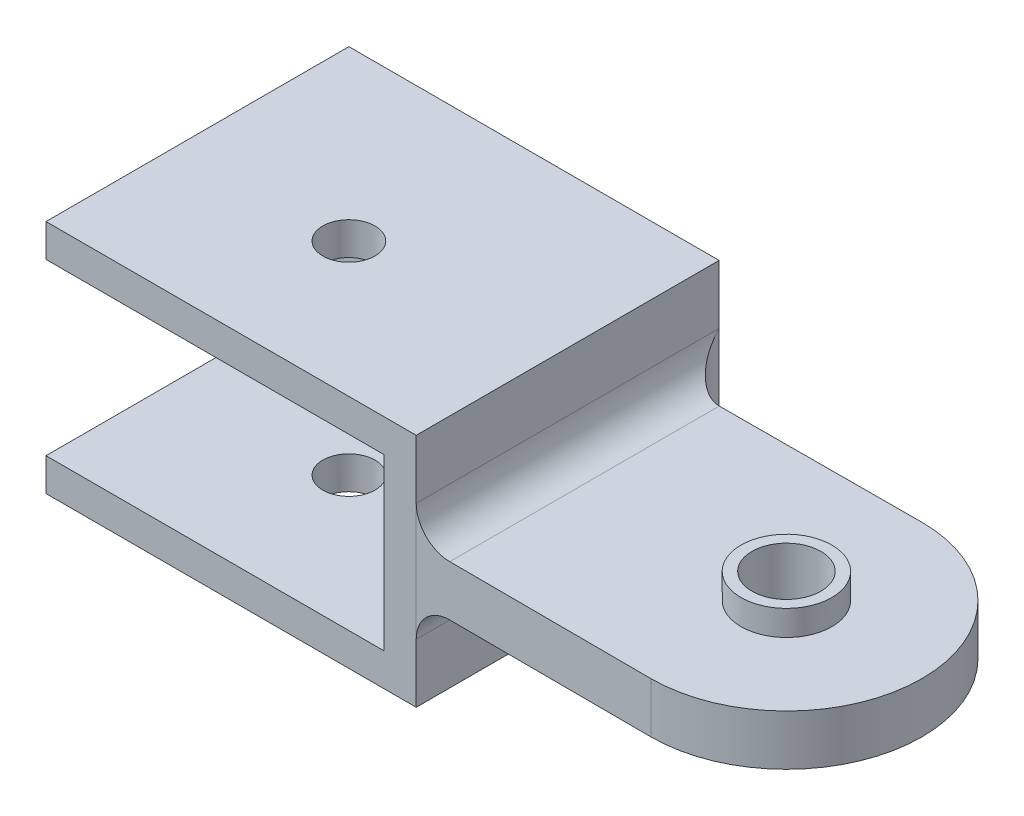
SolidWorks part; units mm, degrees
material "1060 Alloy"
ref_plane "Front Plane" through (0, 0, 0) normal (0, 0, 1) x (1, 0, 0)
ref_plane "Top Plane" through (0, 0, 0) normal (0, 1, 0) x (1, 0, 0)
ref_plane "Right Plane" through (0, 0, 0) normal (1, 0, 0) x (0, 0, -1)
sketch "Sketch1" plane through (0, 0, 0) normal (0, 1, 0) x (1, 0, 0)
  line L0 (0, 0) -> (0, 30319.3642) construction
  line L1 (-12, 8) -> (0, 8)
  line L2 (-12, 8) -> (-12, -8)
  line L3 (-12, -8) -> (0, -8)
  line L4 (0, 8) -> (0, -8)
  line L5 (0, 0) -> (30319.3642, 0) construction
  point P11 (0, -8)
  dimension "D1" = 12
  dimension "D2" = 16
extrude "Boss-Extrude1" add sketch "Sketch1" along normal mid plane 14
ref_plane "Plane1" through (0, 0, 0) normal (0, -1, 0) x (-1, 0, 0)
sketch "Sketch3" plane through (0, 0, 0) normal (0, -1, 0) x (-1, 0, 0)
  line L0 (0, 0) -> (-50000, 0) construction
  line L1 (-14, -8.05) -> (0, -8)
  line L2 (0, -8) -> (0, 8)
  line L3 (0, 8) -> (-14, 8.05)
  circle A0 centre (-14, 0) radius 2.05
  circle A1 centre (-14, 0) radius 8.05 construction
  arc A2 (-14, -8.05) -> (-14, 8.05) centre (-14, 0) cw
  point P5 (-16.05, 0)
  point P7 (-22.05, 0)
  dimension "D1" = 4.1
  dimension "D2" = 14
  dimension "D3" = 6
extrude "Boss-Extrude2" add sketch "Sketch3" along normal mid plane 3
sketch "Sketch4" plane through (-12, 0, 0) normal (-1, 0, 0) x (0, 0, 1)
  line L0 (-8, 7) -> (-8, -7) construction
  line L1 (-8, -5.05) -> (8, -5.05)
  line L2 (-8, -5.05) -> (-8, 5.05)
  line L3 (-8, 5.05) -> (8, 5.05)
  line L4 (8, -5.05) -> (8, 5.05)
  line L5 (8, 7) -> (8, -7) construction
  line L6 (0, 0) -> (50000, 0) construction
  dimension "D1" = 10.1
extrude "Cut-Extrude1" cut sketch "Sketch4" against normal blind 10.1
fillet "Fillet1" radius 2 2 edges at (0, -1.5, 0) (0, 1.5, 0)
sketch "Sketch5" plane through (0, -1.5, 0) normal (0, -1, 0) x (1, 0, 0)
  circle A0 centre (14, 0) radius 2.7
  circle A1 centre (14, 0) radius 2.05
  circle A2 centre (14, 0) radius 2.05 construction
  dimension "D1" = 5.4
extrude "Boss-Extrude3" add sketch "Sketch5" along normal blind 1.5
mirror "Mirror1" about plane through (0, 0, 0) normal (0, -1, 0) of "Boss-Extrude3"
sketch "Sketch8" plane through (-12, 0, 0) normal (-1, 0, 0) x (0, 0, 1)
  line L1 (-8, 7) -> (8, 7)
  line L2 (-8, 7) -> (-8, 5.05)
  line L3 (-8, 5.05) -> (8, 5.05)
  line L4 (8, 7) -> (8, 5.05)
  line L5 (-8, -5.05) -> (8, -5.05)
  line L6 (-8, -5.05) -> (-8, -7)
  line L7 (-8, -7) -> (8, -7)
  line L8 (8, -5.05) -> (8, -7)
extrude "Boss-Extrude4" add sketch "Sketch8" along normal blind 10
sketch "Sketch9" plane through (0, 0, -8) normal (0, 0, -1) x (-1, 0, 0)
  line L1 (0, 7) -> (22, 7)
  line L2 (0, 7) -> (0, -7)
  line L3 (0, -7) -> (22, -7)
  line L4 (22, 7) -> (22, -7)
extrude "Boss-Extrude5" add sketch "Sketch9" along normal blind 2
sketch "Sketch6" plane through (0, 7, 0) normal (0, 1, 0) x (1, 0, 0)
  circle A1 centre (-12, 0) radius 1.55
  circle A3 centre (-12, 0) radius 1.55 construction
extrude "Cut-Extrude2" cut sketch "Sketch6" against normal up to surface (14 mm away) up to face at (-11, -7, -1)
sketch "Sketch10" plane through (0, 0, -8) normal (0, 0, 1) x (1, 0, 0)
  line L1 (-22, 5.05) -> (-1.9, 5.05)
  line L2 (-22, 5.05) -> (-22, -5.05)
  line L3 (-22, -5.05) -> (-1.9, -5.05)
  line L4 (-1.9, 5.05) -> (-1.9, -5.05)
extrude "Cut-Extrude3" cut sketch "Sketch10" against normal blind 0.1
sketch "Sketch11" plane through (0, 0, 0) normal (0, -1, 0) x (-1, 0, 0)
  line L0 (-14, 0) -> (-11.95, 0) construction
  line L1 (-14, 0) -> (-14, 2.05) construction
  circle A0 centre (-14, 0) radius 2.05 construction
fillet "Fillet2" radius 2 1 edges at (0, 0, -8)
